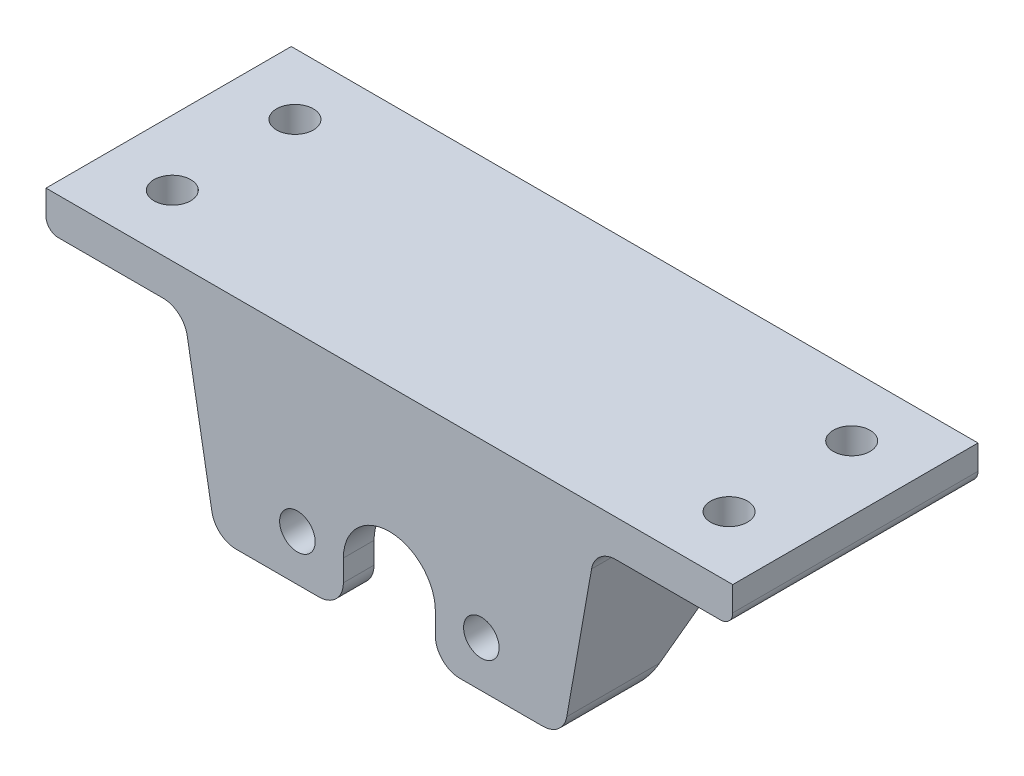
SolidWorks part; units mm, degrees
material "ABS"
ref_plane "Front Plane" through (0, 0, 0) normal (0, 0, 1) x (1, 0, 0)
ref_plane "Top Plane" through (0, 0, 0) normal (0, 1, 0) x (1, 0, 0)
ref_plane "Right Plane" through (0, 0, 0) normal (1, 0, 0) x (0, 0, -1)
sketch "Motor Profile" plane through (0, 0, 0) normal (0, 0, 1) x (1, 0, 0)
  circle A0 centre (0, 0) radius 10 construction
  circle A1 centre (-7.5, 0) radius 1 construction
  circle A2 centre (7.5, 0) radius 1 construction
  circle A3 centre (0, 0) radius 3.5 construction
  dimension "D1" = 7
  dimension "D2" = 2
  dimension "D3" = 20
  dimension "D4" = 2
  dimension "D5" = 15
  dimension "D6" = 7.5
sketch "Sketch2" plane through (0, 0, 0) normal (0, 0, 1) x (1, 0, 0)
  line L0 (-3.75, 0) -> (-3.75, -1.75)
  line L1 (3.75, 0) -> (3.75, -1.75)
  line L2 (-5.75, -3.75) -> (-12.5, -3.75)
  line L3 (-14.4696, -2.0973) -> (-16.4876, 9.3473)
  line L4 (5.75, -3.75) -> (12.5, -3.75)
  line L5 (14.4696, -2.0973) -> (16.4876, 9.3473)
  line L7 (-18.4572, 11) -> (-27, 11)
  line L8 (18.4572, 11) -> (27, 11)
  line L9 (-28, 12) -> (-28, 14)
  line L10 (-28, 14) -> (28, 14)
  line L11 (28, 14) -> (28, 12)
  arc A0 (3.75, 0) -> (-3.75, 0) centre (0, 0) ccw
  circle A1 centre (-7.5, 0) radius 1.45
  circle A2 centre (7.5, 0) radius 1.45
  arc A3 (-5.75, -3.75) -> (-3.75, -1.75) centre (-5.75, -1.75) ccw
  arc A4 (5.75, -3.75) -> (3.75, -1.75) centre (5.75, -1.75) cw
  arc A5 (-12.5, -3.75) -> (-14.4696, -2.0973) centre (-12.5, -1.75) cw
  arc A6 (14.4696, -2.0973) -> (12.5, -3.75) centre (12.5, -1.75) cw
  arc A8 (-16.4876, 9.3473) -> (-18.4572, 11) centre (-18.4572, 9) ccw
  arc A9 (16.4876, 9.3473) -> (18.4572, 11) centre (18.4572, 9) cw
  arc A10 (-27, 11) -> (-28, 12) centre (-27, 12) cw
  arc A11 (28, 12) -> (27, 11) centre (27, 12) cw
  point P20 (-3.75, -3.75)
  point P23 (3.75, -3.75)
  point P27 (-14.1782, -3.75)
  point P33 (-16.779, 11)
  point P36 (16.779, 11)
  point P39 (-28, 11)
  dimension "D1" = 7.5
  dimension "D2" = 2.9
  dimension "D7" = 2
  dimension "D8" = 2
  dimension "D9" = 2
  dimension "D10" = 2
  dimension "D13" = 2
  dimension "D14" = 2
  dimension "D16" = 1
  dimension "D17" = 1
  dimension "D4" = 3.75
  dimension "D3" = 80
  dimension "D5" = 80
  dimension "D6" = 5
  dimension "D11" = 11
  dimension "D12" = 3
  dimension "D15" = 56
extrude "Boss-Extrude1" add sketch "Sketch2" against normal blind 2.5
ref_plane "Plane2" through (0, 0, -20) normal (0, 0, 1) x (1, 0, 0)
sketch "Sketch3" plane through (0, 0, -2.5) normal (0, 0, -1) x (-1, 0, 0)
  line L11 (-11, -2.75) -> (-11, 6)
  line L12 (-5.75, -3.75) -> (-12.5, -3.75) construction
  line L13 (-6, 11) -> (6, 11)
  line L14 (11, 6) -> (11, -2.75)
  line L15 (12.5, -3.75) -> (5.75, -3.75) construction
  line L16 (12, -3.75) -> (12.5, -3.75)
  line L17 (-12, -3.75) -> (-12.5, -3.75)
  line L22 (3.75, 0) -> (3.75, -1.75)
  line L23 (5.75, -3.75) -> (12.5, -3.75)
  line L24 (14.4696, -2.0973) -> (16.4876, 9.3473)
  line L25 (18.4572, 11) -> (27, 11)
  line L26 (28, 12) -> (28, 14)
  line L27 (28, 14) -> (-28, 14)
  line L28 (-28, 14) -> (-28, 12)
  line L29 (-27, 11) -> (-18.4572, 11)
  line L30 (-16.4876, 9.3473) -> (-14.4696, -2.0973)
  line L31 (-12.5, -3.75) -> (-5.75, -3.75)
  line L32 (-3.75, -1.75) -> (-3.75, 0)
  line L35 (14.4696, -2.0973) -> (16.4876, 9.3473)
  line L36 (18.4572, 11) -> (27, 11)
  line L37 (28, 12) -> (28, 14)
  line L38 (28, 14) -> (-28, 14)
  line L39 (-28, 14) -> (-28, 12)
  line L40 (-27, 11) -> (-18.4572, 11)
  line L41 (-16.4876, 9.3473) -> (-14.4696, -2.0973)
  arc A9 (-11, 6) -> (-6, 11) centre (-6, 6) cw
  arc A10 (11, 6) -> (6, 11) centre (6, 6) ccw
  arc A11 (-11, -2.75) -> (-12, -3.75) centre (-12, -2.75) cw
  arc A12 (12, -3.75) -> (11, -2.75) centre (12, -2.75) cw
  arc A18 (3.75, 0) -> (-3.75, 0) centre (0, 0) ccw
  arc A19 (3.75, -1.75) -> (5.75, -3.75) centre (5.75, -1.75) ccw
  arc A20 (12.5, -3.75) -> (14.4696, -2.0973) centre (12.5, -1.75) ccw
  arc A21 (18.4572, 11) -> (16.4876, 9.3473) centre (18.4572, 9) ccw
  arc A22 (27, 11) -> (28, 12) centre (27, 12) ccw
  arc A23 (-28, 12) -> (-27, 11) centre (-27, 12) ccw
  arc A24 (-16.4876, 9.3473) -> (-18.4572, 11) centre (-18.4572, 9) ccw
  arc A25 (-14.4696, -2.0973) -> (-12.5, -3.75) centre (-12.5, -1.75) ccw
  arc A26 (-5.75, -3.75) -> (-3.75, -1.75) centre (-5.75, -1.75) ccw
  arc A29 (12.5, -3.75) -> (14.4696, -2.0973) centre (12.5, -1.75) ccw
  arc A30 (18.4572, 11) -> (16.4876, 9.3473) centre (18.4572, 9) ccw
  arc A31 (27, 11) -> (28, 12) centre (27, 12) ccw
  arc A32 (-28, 12) -> (-27, 11) centre (-27, 12) ccw
  arc A33 (-16.4876, 9.3473) -> (-18.4572, 11) centre (-18.4572, 9) ccw
  arc A34 (-14.4696, -2.0973) -> (-12.5, -3.75) centre (-12.5, -1.75) ccw
  point P7 (0, 11)
  point P26 (-11, -3.75)
  point P29 (11, -3.75)
  dimension "D3" = 5
  dimension "D4" = 5
  dimension "D5" = 1
  dimension "D6" = 1
  dimension "D2" = 11
  dimension "D1" = 0
extrude "Boss-Extrude2" add sketch "Sketch3" along direction (0, 0, 1) on the side of the normal up to surface (17.5 mm away) up to plane "Plane2"
sketch "Sketch6" plane through (0, 0, 0) normal (1, 0, 0) x (0, 0, -1)
  line L0 (6, -3.75) -> (20, 11)
  line L1 (20, -3.75) -> (0, -3.75) construction
  line L2 (20, 9.7625) -> (20, -9.7625) construction
  line L3 (20, 11) -> (0, 11) construction
  line L4 (6, -3.75) -> (20, -3.75)
  line L5 (20, -3.75) -> (20, 11)
  dimension "D1" = 6
extrude "Cut-Extrude1" cut sketch "Sketch6" against normal through all both and the other way through all
sketch "Sketch9" plane through (0, 11, 0) normal (0, -1, 0) x (1, 0, 0)
  line L0 (18.4572, -20) -> (27, -20) construction
  line L1 (28, -20) -> (28, 0) construction
  line L3 (18.4572, 0) -> (27, 0) construction
  circle A0 centre (22.7, -15) radius 1.5
  circle A1 centre (22.7, -5) radius 1.5
  dimension "D1" = 3
  dimension "D2" = 5
  dimension "D3" = 5
  dimension "D4" = 5.3
extrude "Cut-Extrude2" cut sketch "Sketch9" against normal through all
mirror "Mirror1" about plane through (0, 0, 0) normal (1, 0, 0) of "Cut-Extrude2"
ref_point "Point1"
ref_point "Point2"
ref_axis "Axis1" through (7.5, 0, -2.5) along (-1, 0, 0)
sketch "Sketch10" plane through (0, 0, -2.5) normal (0, 0, -1) x (-1, 0, 0)
  circle A0 centre (0, 0) radius 10.432
split line "Split Line1"
equation "\"D6@Motor Profile\" = \"D5@Motor Profile\" / 2"
equation "\"D5@Sketch2\"=\"D3@Sketch2\""
